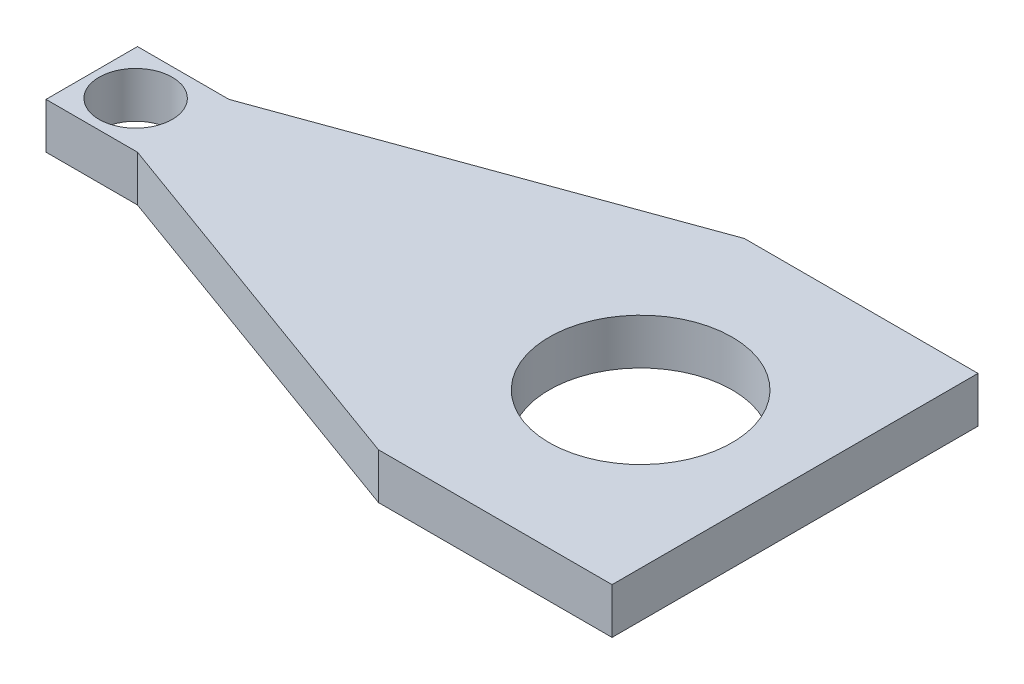
SolidWorks part; units mm, degrees
ref_plane "Front Plane" through (0, 0, 0) normal (0, 0, 1) x (1, 0, 0)
ref_plane "Top Plane" through (0, 0, 0) normal (0, 1, 0) x (1, 0, 0)
ref_plane "Right Plane" through (0, 0, 0) normal (1, 0, 0) x (0, 0, -1)
sketch "Sketch1" plane through (0, 0, 0) normal (0, 1, 0) x (1, 0, 0)
  line L0 (-15.875, 1.5875) -> (-2.7496, 6.35)
  line L4 (-19.05, 1.5875) -> (-19.05, -1.5875)
  line L5 (-15.875, 1.5875) -> (-19.05, 1.5875)
  line L7 (-15.875, -1.5875) -> (-19.05, -1.5875)
  line L8 (-19.05, 1.5875) -> (-19.05, -1.5875)
  line L9 (-19.05, 1.5875) -> (-15.875, 1.5875)
  line L10 (-19.05, 1.5875) -> (-19.05, -1.5875)
  line L11 (-19.05, -1.5875) -> (-15.875, -1.5875)
  line L12 (-15.875, 1.5875) -> (-15.875, -1.5875)
  line L13 (5.358, 6.35) -> (-2.7496, 6.35)
  line L14 (5.358, 6.35) -> (5.358, -6.35)
  line L15 (5.358, -6.35) -> (-2.7496, -6.35)
  line L16 (-19.05, 1.5875) -> (-19.05, -1.5875)
  line L17 (-15.875, -1.5875) -> (-2.7496, -6.35)
  arc A0 (-2.7496, -1.5875) -> (-2.7496, 1.5875) centre (0, 0) ccw
  circle A2 centre (-17.526, 0) radius 1.27
  circle A3 centre (0, 0) radius 3.175
  dimension "D1" = 6.35
  dimension "D4" = 6.35
  dimension "D3" = 1.524
  dimension "D2" = 3.175
  dimension "D5" = 6.35
extrude "Boss-Extrude1" add sketch "Sketch1" along normal blind 1.5875 contours L12 L17 L15 L14 L13 L0 A3 A0 | L12 L5 L4 L7 A2 region at (-15.9199, 0, 0) region at (-3.9842, 0, 0)
